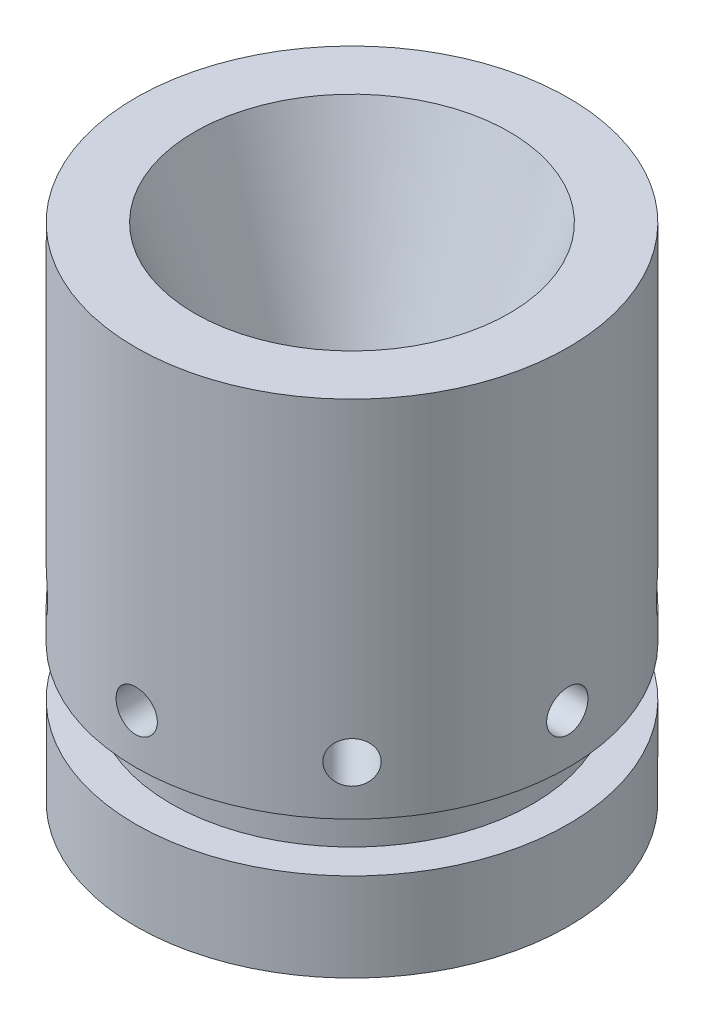
SolidWorks part; units mm, degrees
ref_plane "Front" through (0, 0, 0) normal (0, 0, 1) x (1, 0, 0)
ref_plane "Top" through (0, 0, 0) normal (0, 1, 0) x (1, 0, 0)
ref_plane "Right" through (0, 0, 0) normal (1, 0, 0) x (0, 0, -1)
sketch "Sketch2" plane through (0, 0, 0) normal (0, 0, 1) x (1, 0, 0)
  line L0 (0, 19.1415) -> (0, -24.752) construction
  line L1 (-15.8413, 0) -> (18.4815, 0) construction
  line L2 (-15.8413, 2) -> (18.4815, 2) construction
  line L3 (-2.5, 0) -> (-2.5, 2)
  line L4 (-11, 21.0703) -> (-11, -1.5) construction
  line L5 (-2.5, 0) -> (-11, -8.5)
  line L6 (-11, -8.5) -> (-11, -4)
  line L7 (-18.3668, 17) -> (19.9717, 17) construction
  line L8 (-2.5, 2) -> (-8, 17)
  line L9 (-8, 17) -> (-11, 17)
  line L10 (-11, 17) -> (-11, 2)
  line L11 (-11, -1.5) -> (-11, 2)
  line L12 (-11, -1.5) -> (-9.2, -1.5)
  line L14 (-11, -4) -> (-9.2, -4)
  line L15 (-9.2, -1.5) -> (-9.2, -4)
  line L16 (-11, -4) -> (-11, -24.752) construction
  dimension "D1" = 11
  dimension "D2" = 2
  dimension "D3" = 45
  dimension "D4" = 15
  dimension "D5" = 2.5
  dimension "ThrottleRadius" = 2.5
  dimension "NozzleRadius" = 8
  dimension "D6" = 1.8
  dimension "D7" = 1.5
revolve "Revolve1" add sketch "Sketch2" angle 360 about L0
ref_plane "Plane1" through (-11, 0, 0) normal (-1, 0, 0) x (0, 0, 1)
sketch "Sketch3" plane through (-11, 0, 0) normal (-1, 0, 0) x (0, 0, 1)
  line L0 (0, 17) -> (0, -8.4987) construction
  line L1 (8, 17) -> (-8, 17) construction
  line L2 (11, 17) -> (-11, 17) construction
  circle A0 centre (0, 1) radius 1.05
  dimension "D1" = 2.1
  dimension "D2" = 16
extrude "Cut-Extrude1" cut sketch "Sketch3" against normal blind 6
ref_axis "Axis1" through (0, 0, 0) along (0, 1, 0)
pattern_circular "CirPattern1" count 8 over 360 about axis through (0, 0, 0) along (0, 1, 0) of "Cut-Extrude1"
